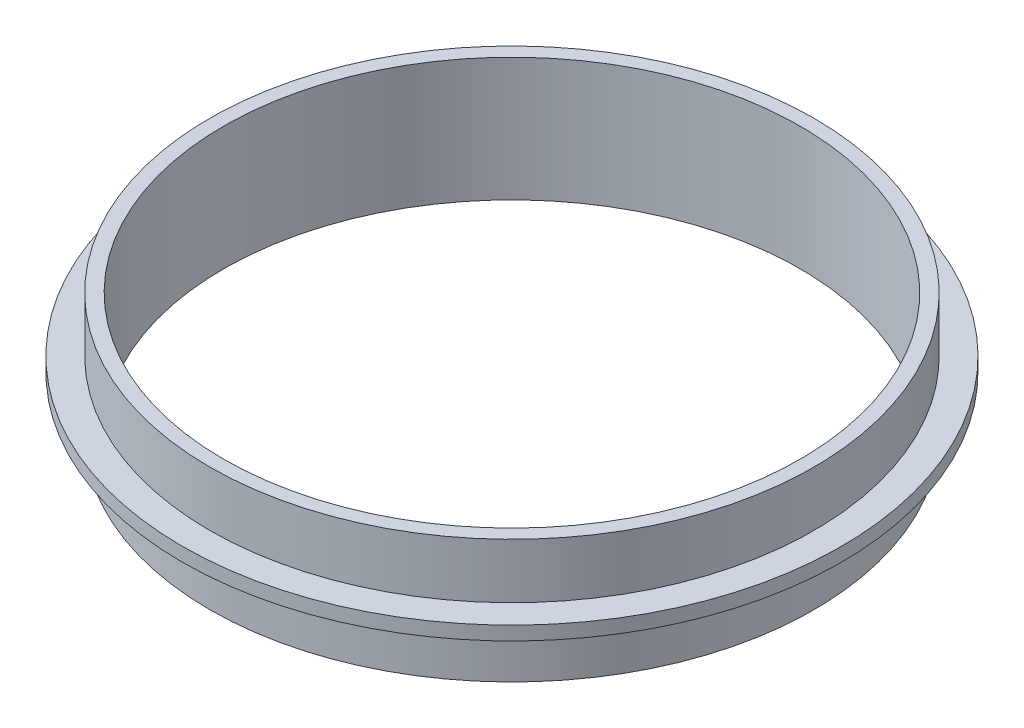
SolidWorks part; units mm, degrees
material "6061-T6 (SS)"
ref_plane "Front Plane" through (0, 0, 0) normal (0, 0, 1) x (1, 0, 0)
ref_plane "Top Plane" through (0, 0, 0) normal (0, 1, 0) x (1, 0, 0)
ref_plane "Right Plane" through (0, 0, 0) normal (1, 0, 0) x (0, 0, -1)
sketch "Sketch2" plane through (0, 0, 0) normal (0, 1, 0) x (1, 0, 0)
  circle A0 centre (0, 0) radius 152.4
  circle A1 centre (0, 0) radius 133.35
  dimension "D1" = 266.7
  dimension "D2" = 304.8
extrude "Boss-Extrude1" add sketch "Sketch2" along normal blind 3.175 and the other way blind 3.175
sketch "Sketch3" plane through (0, 3.175, 0) normal (0, 1, 0) x (1, 0, 0)
  circle A0 centre (0, 0) radius 139.7
  circle A1 centre (0, 0) radius 133.35 construction
  circle A2 centre (0, 0) radius 133.35
  dimension "D1" = 279.4
extrude "Boss-Extrude2" add sketch "Sketch3" along normal blind 25.4
mirror "Mirror1" about plane through (0, 0, 0) normal (0, 1, 0) of "Boss-Extrude2"
